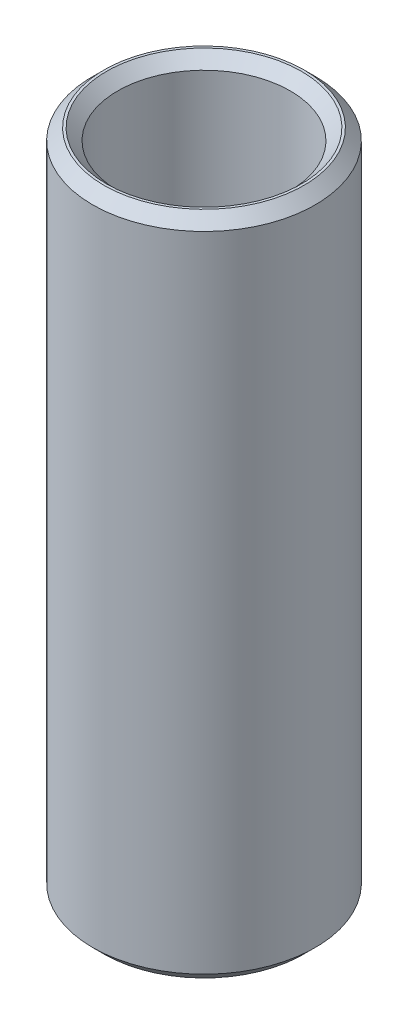
SolidWorks part; units mm, degrees
ref_plane "Front Plane" through (0, 0, 0) normal (0, 0, 1) x (1, 0, 0)
ref_plane "Top Plane" through (0, 0, 0) normal (0, 1, 0) x (1, 0, 0)
ref_plane "Right Plane" through (0, 0, 0) normal (1, 0, 0) x (0, 0, -1)
sketch "Sketch1" plane through (0, 0, 0) normal (0, 1, 0) x (1, 0, 0)
  circle A0 centre (0, 0) radius 12.5
  dimension "SLEEVE_OD" = 25
extrude "Boss-Extrude1" add sketch "Sketch1" along normal blind 74.7827
sketch "Sketch2" plane through (0, 0, 0) normal (0, 1, 0) x (1, 0, 0)
  circle A0 centre (0, 0) radius 9.6923
  dimension "BORE_D" = 19.3845
extrude "Cut-Extrude1" cut sketch "Sketch2" along normal through all
chamfer "Chamfer1" distance 1.2642 angle 45 4 edges at (0, 74.7827, 9.6923) (0, 0, 9.6923) (0, 0, 12.5) (0, 74.7827, 12.5)
